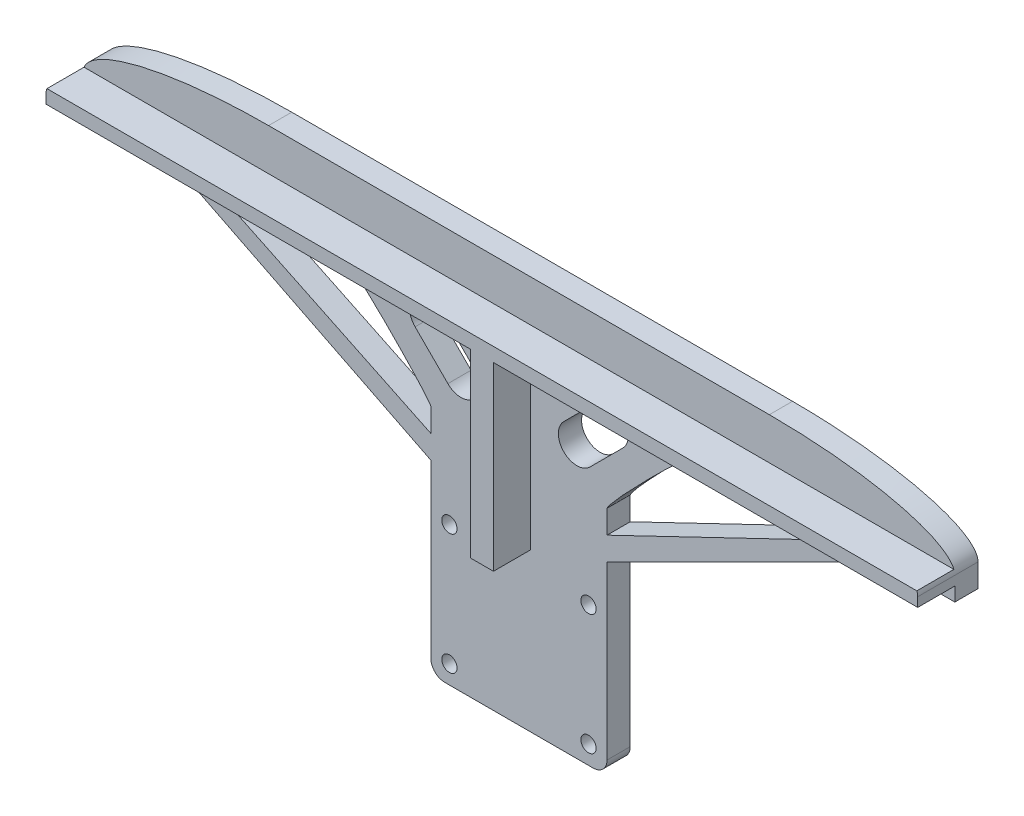
SolidWorks part; units mm, degrees
ref_plane "Front" through (0, 0, 0) normal (0, 0, 1) x (1, 0, 0)
ref_plane "Top" through (0, 0, 0) normal (0, 1, 0) x (1, 0, 0)
ref_plane "Right" through (0, 0, 0) normal (1, 0, 0) x (0, 0, -1)
sketch "Sketch1" plane through (0, 0, 0) normal (0, 0, 1) x (1, 0, 0)
  line L0 (38, 0) -> (113, 0)
  line L1 (0, 0) -> (38, 0)
  line L2 (0, 0) -> (0, -70)
  line L3 (0, -70) -> (38, -70)
  line L4 (38, 0) -> (38, -70)
  line L5 (113, 0) -> (113, 15)
  line L6 (113, 15) -> (-75, 15)
  line L7 (-75, 15) -> (-75, 0)
  line L8 (-75, 0) -> (0, 0)
  dimension "D1" = 38
  dimension "D2" = 70
  dimension "D3" = 75
  dimension "D4" = 75
  dimension "D5" = 15
extrude "Boss-Extrude1" add sketch "Sketch1" along normal blind 5 contours L4 L1 L2 L3 | L7 L8 L1 L0 L5 L6 region at (19, 7.5, 0) region at (19, -35, 0)
sketch "Sketch2" plane through (0, 0, 5) normal (0, 0, 1) x (1, 0, 0)
  line L0 (38, 0) -> (38, -70) construction
  line L1 (0, -70) -> (38, -70) construction
  circle A0 centre (34, -66) radius 1.65
  circle A1 centre (4, -66) radius 1.65
  circle A2 centre (4, -40) radius 1.65
  circle A3 centre (34, -40) radius 1.65
  dimension "D1" = 3.3
  dimension "D2" = 4
  dimension "D3" = 4
  dimension "D4" = 2
  dimension "D5" = 2
extrude "Cut-Extrude1" cut sketch "Sketch2" against normal through all
fillet "Fillet1" radius 3 2 edges at (38, -70, 2.5) (0, -70, 2.5)
fillet "Fillet2" radius 20 2 edges at (0, 0, 2.5) (38, 0, 2.5) conic rho 0.05
sketch "Sketch3" plane through (0, 0, 5) normal (0, 0, 1) x (1, 0, 0)
  line L0 (-75, 15) -> (-75, 0) construction
  line L1 (-75, 3) -> (113, 3)
  line L2 (-75, 3) -> (-75, 6)
  line L3 (-75, 6) -> (113, 6)
  line L4 (113, 3) -> (113, 6)
  line L5 (113, 0) -> (113, 15) construction
  dimension "D1" = 3
  dimension "D2" = 12
extrude "Boss-Extrude2" add sketch "Sketch3" along normal blind 8
sketch "Sketch4" plane through (0, 0, 5) normal (0, 0, 1) x (1, 0, 0)
  line L0 (-75, 3) -> (113, 3) construction
  line L1 (16.5, 3) -> (21.5, 3)
  line L2 (16.5, 3) -> (16.5, -36)
  line L3 (16.5, -36) -> (21.5, -36)
  line L4 (21.5, 3) -> (21.5, -36)
  line L5 (0, -20) -> (0, -67) construction
  dimension "D1" = 39
  dimension "D2" = 5
  dimension "D3" = 16.5
extrude "Boss-Extrude3" add sketch "Sketch4" along normal blind 8
sketch "Sketch5" plane through (0, 0, 5) normal (0, 0, 1) x (1, 0, 0)
  line L0 (90, 0) -> (38, -25)
  line L1 (58, 0) -> (113, 0) construction
  line L2 (38, -20) -> (38, -67) construction
  line L3 (38, -25) -> (38, -30)
  line L4 (38, -30) -> (98, 0)
  line L5 (98, 0) -> (90, 0)
  line L6 (-57.903, 0) -> (-52, 0)
  line L7 (-75, 0) -> (-20, 0) construction
  line L8 (-52, 0) -> (0, -25)
  line L9 (0, -20) -> (0, -67) construction
  line L10 (0, -25) -> (0, -30)
  line L11 (0, -30) -> (-60, 0)
  line L12 (-60, 0) -> (-52, 0)
  line L13 (-52, 0) -> (-52.0215, 0.2507)
  line L14 (113, 0) -> (113, 3) construction
  line L15 (-75, 3) -> (-75, 0) construction
  line M12 (-75, 0) -> (-20, 0)
  line M14 (0, -20) -> (0, -67)
  dimension "D1" = 15
  dimension "D2" = 8
  dimension "D3" = 5
  dimension "D4" = 5
  dimension "D5" = 5
  dimension "D6" = 5
  dimension "D7" = 15
  dimension "D8" = 8
extrude "Boss-Extrude4" add sketch "Sketch5" against normal blind 5 contours L11 L8 M14 M12 | L4 L5 L0 L3 region at (-26.9333, -14.3333, 5)
fillet "Fillet3" radius 40 1 edges at (-75, 15, 2.5) second distance 10 first distance on face at (19, 15, 2.5)
fillet "Fillet4" radius 10 1 edges at (113, 15, 2.5) second distance 40 first distance on face at (113, 6, 5.75)
sketch "Sketch6" plane through (0, 0, 5) normal (0, 0, 1) x (1, 0, 0)
  line L0 (6.5, -11.034) -> (-0.5711, -3.9629) construction
  line L1 (3.6716, -13.8624) -> (-3.3995, -6.7913)
  line L2 (9.3284, -8.2056) -> (2.2574, -1.1345)
  line L3 (31.5, -11.2734) -> (38.5711, -4.2024) construction
  line L4 (28.6716, -8.445) -> (35.7426, -1.3739)
  line L5 (34.3284, -14.1019) -> (41.3995, -7.0308)
  line L6 (16.5, 3) -> (16.5, -36) construction
  line L7 (21.5, -36) -> (21.5, 3) construction
  arc A0 (3.6716, -13.8624) -> (9.3284, -8.2056) centre (6.5, -11.034) ccw
  arc A1 (2.2574, -1.1345) -> (-3.3995, -6.7913) centre (-0.5711, -3.9629) ccw
  arc A2 (28.6716, -8.445) -> (34.3284, -14.1019) centre (31.5, -11.2734) ccw
  arc A3 (41.3995, -7.0308) -> (35.7426, -1.3739) centre (38.5711, -4.2024) ccw
  point P2 (2.9645, -7.4984)
  point P7 (35.0355, -7.7379)
  dimension "D1" = 4
  dimension "D2" = 4
  dimension "D3" = 10
  dimension "D4" = 10
  dimension "D5" = 10
  dimension "D6" = 10
extrude "Cut-Extrude2" cut sketch "Sketch6" against normal through all
equation "\"滑动-垂直孔\" = 0.6"
equation "\"滑动-水平孔\"= 0.3"
equation "\"松动-垂直孔\" = 0.3"
equation "\"松动-水平孔\"= 0.1"
equation "\"正常-垂直孔\" = 0.15"
equation "\"正常-水平孔\"= 0"
equation "\"紧缩-垂直孔\"= 0"
equation "\"紧缩-水平孔\"= - 0.1"
equation "\"D1@Sketch2\"=\"松动-垂直孔\"+3"
